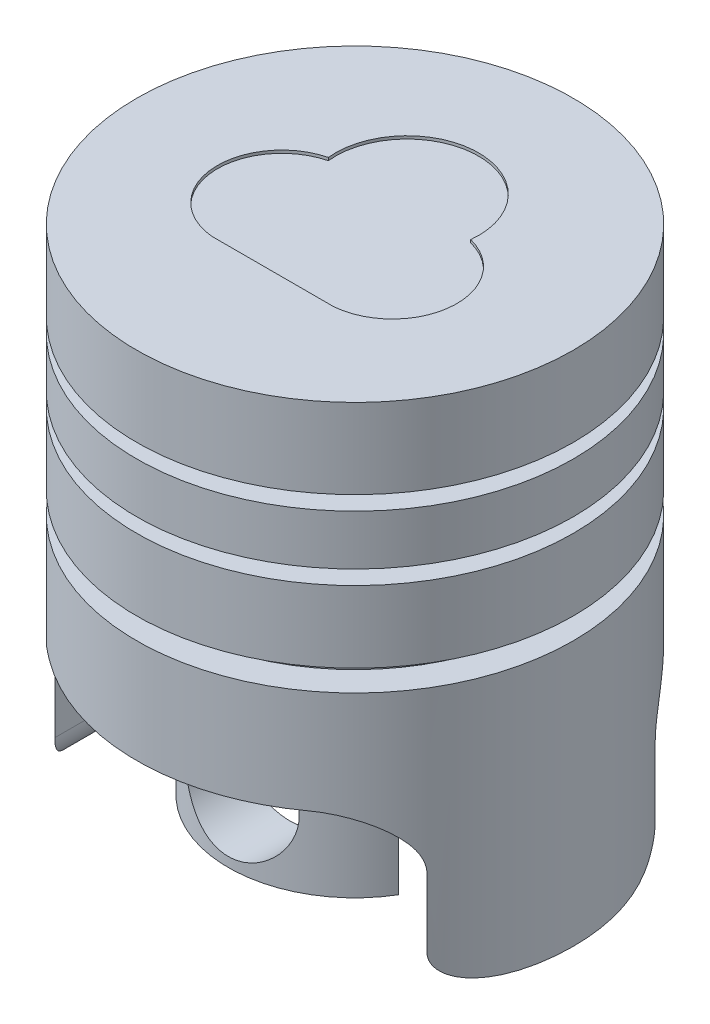
SolidWorks part; units mm, degrees
ref_plane "Front Plane" through (0, 0, 0) normal (0, 0, 1) x (1, 0, 0)
ref_plane "Top Plane" through (0, 0, 0) normal (0, 1, 0) x (1, 0, 0)
ref_plane "Right Plane" through (0, 0, 0) normal (1, 0, 0) x (0, 0, -1)
sketch "Sketch1" plane through (0, 0, 0) normal (0, 0, 1) x (1, 0, 0)
  line L0 (0, 39.2513) -> (0, 22.9529) construction
  line L1 (0, 35.9529) -> (-30.5, 35.9529)
  line L2 (-30.5, 35.9529) -> (-30.5, 24.7929)
  line L3 (-30.5, 24.7929) -> (-26.5, 24.7929)
  line L4 (-26.5, 24.7929) -> (-26.5, 22.7929)
  line L5 (-26.5, 22.7929) -> (-30.5, 22.7929)
  line L6 (-30.5, 22.7929) -> (-30.5, 15.7929)
  line L7 (-30.5, 15.7929) -> (-26.5, 15.7929)
  line L8 (-26.5, 15.7929) -> (-26.5, 13.7929)
  line L9 (-26.5, 13.7929) -> (-30.5, 13.7929)
  line L10 (-30.5, 13.7929) -> (-30.5, 3.7929)
  line L11 (-30.5, 3.7929) -> (-26.5, 3.7929)
  line L12 (-26.5, 3.7929) -> (-26.5, 0.7929)
  line L13 (-26.5, 0.7929) -> (-30.5, 0.7929)
  line L14 (-30.5, 0.7929) -> (-30.5, -36.2071)
  line L15 (-30.5, -36.2071) -> (-17.7, -36.2071)
  line L16 (0, 22.9529) -> (0, 35.9529)
  line L17 (-17.7, -36.2071) -> (-17.7, 22.9529)
  line L18 (-17.7, 22.9529) -> (0, 22.9529)
  dimension "D1" = 30.5
  dimension "D2" = 13
  dimension "D3" = 4
  dimension "D4" = 2
  dimension "D5" = 7
  dimension "D6" = 10
  dimension "D7" = 3
  dimension "D8" = 37
  dimension "D9" = 12.8
  dimension "D10" = 59.16
revolve "Revolve1" add sketch "Sketch1" angle 360 about L0
sketch "Sketch2" plane through (0, 0, 0) normal (0, 0, 1) x (1, 0, 0)
  line L0 (-30.5, -36.2071) -> (30.5, -36.2071) construction
  line L1 (-26, -58.7071) -> (26, -58.7071)
  line L2 (-26, -58.7071) -> (-26, -13.7071)
  line L3 (-26, -13.7071) -> (26, -13.7071)
  line L4 (26, -58.7071) -> (26, -13.7071)
  line L5 (-26, -58.7071) -> (26, -13.7071) construction
  line L6 (-26, -13.7071) -> (26, -58.7071) construction
  point P0 (0, -36.2071)
  dimension "D1" = 52
  dimension "D2" = 45
extrude "Cut-Extrude1" cut sketch "Sketch2" against normal through all both and the other way through all
fillet "Fillet1" radius 8 2 edges at (26, -13.7071, 0) (-26, -13.7071, 0)
sketch "Sketch3" plane through (0, 22.9529, 0) normal (0, -1, 0) x (1, 0, 0)
  line L1 (-15.1861, -9.0925) -> (15.1861, -9.0925)
  line L2 (-15.1861, 9.0925) -> (15.1861, 9.0925)
  arc A0 (15.1861, 9.0925) -> (-15.1861, 9.0925) centre (0, 0) ccw
  circle A1 centre (0, 0) radius 17.7
  arc A2 (-15.1861, -9.0925) -> (15.1861, -9.0925) centre (0, 0) ccw
  dimension "D1" = 0
extrude "Boss-Extrude1" add sketch "Sketch3" along normal blind 56
sketch "Sketch4" plane through (0, 0, -9.0925) normal (0, 0, 1) x (1, 0, 0)
  line L0 (0, 3.7929) -> (0, 0.7929)
  line L1 (-26.5, 3.7929) -> (26.5, 3.7929) construction
  line L2 (30.5, 0.7929) -> (-30.5, 0.7929) construction
  circle A0 centre (0, -23.7071) radius 8
  point P3 (0, 2.2929)
  dimension "D2" = 16
  dimension "D1" = 26
extrude "Cut-Extrude2" cut sketch "Sketch4" against normal through all both and the other way through all contours A0 region at (0, -23.7071, -9.0925)
fillet "Fillet2" radius 5 2 edges at (26, -36.2071, 0) (-26, -36.2071, 0)
sketch "Sketch5" plane through (0, 35.9529, 0) normal (0, 1, 0) x (1, 0, 0)
  line L0 (0, 21.2616) -> (0, -25.0102) construction
  line L1 (-8.5, -11.4666) -> (8.5, -11.4666)
  arc A0 (9.9444, 6.2227) -> (-9.9444, 6.2227) centre (0, 7.2761) ccw
  arc A1 (-9.9444, 6.2227) -> (-8.5, -11.4666) centre (-7.7268, -2.4998) ccw
  arc A2 (9.9444, 6.2227) -> (8.5, -11.4666) centre (7.7268, -2.4998) cw
  point P11 (0, -11.4666)
  dimension "D1" = 10
  dimension "D2" = 9
  dimension "D3" = 17
extrude "Cut-Extrude3" cut sketch "Sketch5" against normal blind 0.4
